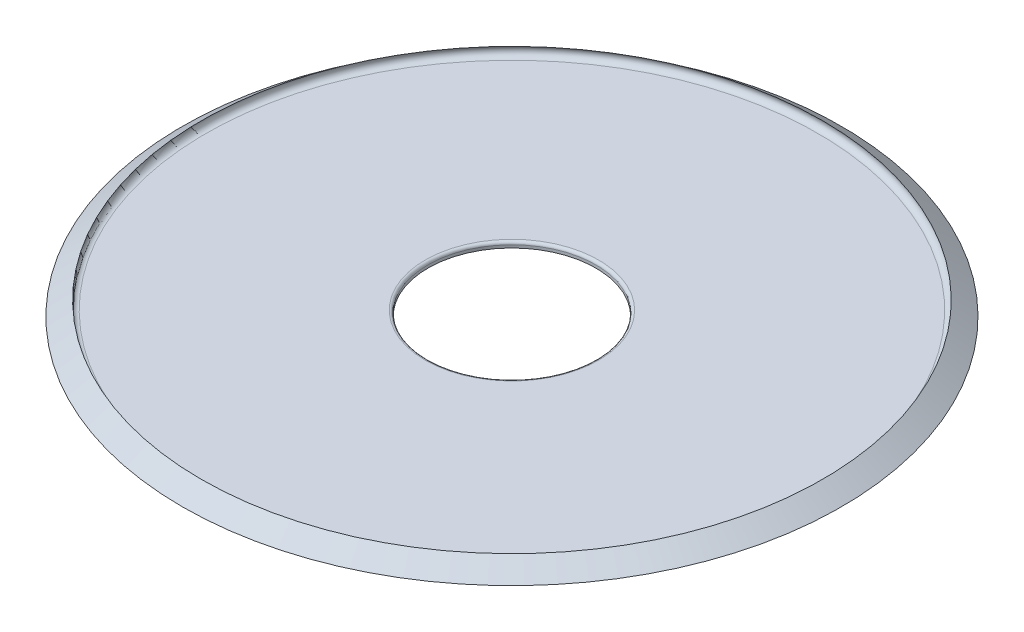
SolidWorks part; units mm, degrees
ref_plane "Front" through (0, 0, 0) normal (0, 0, 1) x (1, 0, 0)
ref_plane "Top" through (0, 0, 0) normal (0, 1, 0) x (1, 0, 0)
ref_plane "Right" through (0, 0, 0) normal (1, 0, 0) x (0, 0, -1)
sketch "Sketch6"
  line L0 (0, 6.1332) -> (0, -2.0816) construction
  line L1 (5.5482, 4.3361) -> (5.8861, 4.08)
  line L2 (1.55, 4.18) -> (5.4653, 4.18)
  line L3 (1.5, 4.13) -> (1.5, 4.08)
  line L4 (1.5, 4.08) -> (5.4929, 4.08)
  line L5 (5.4929, 4.08) -> (5.8861, 4.08)
  line L10 (5.5482, 4.3361) -> (5.8861, 4.08)
  line L11 (5.4929, 4.08) -> (5.8861, 4.08)
  line L12 (0, -16.52) -> (0, -60.6715) construction
  arc A0 (1.5, 4.13) -> (1.55, 4.18) centre (1.55, 4.13) cw
  arc A9 (5.4653, 4.18) -> (5.5482, 4.3361) centre (5.4653, 4.28) ccw
  dimension "D1" = 0.05
sketch "Sketch6<7>" plane through (0, 0, 0) normal (0, 0, 1) x (1, 0, 0) same geometry as "Sketch6"
revolve "iris" add sketch "Sketch6" angle 360 about L0
sketch "Sketch10" plane through (0, 4.18, 0) normal (0, 1, 0) x (1, 0, 0)
  arc A1 (2.6604, 0) -> (2.038, -1.7101) centre (3.2043, -1.1663) ccw
  arc A2 (2.038, -1.7101) -> (0.462, -2.62) centre (1.705, -2.9531) ccw
  arc A3 (0.462, -2.62) -> (-1.3302, -2.304) centre (-0.5921, -3.3581) ccw
  arc A4 (-1.3302, -2.304) -> (-2.5, -0.9099) centre (-2.6122, -2.1919) ccw
  arc A5 (-2.5, -0.9099) -> (-2.5, 0.9099) centre (-3.4099, 0) ccw
  arc A6 (-2.5, 0.9099) -> (-1.3302, 2.304) centre (-2.6122, 2.1919) ccw
  arc A7 (-1.3302, 2.304) -> (0.462, 2.62) centre (-0.5921, 3.3581) ccw
  arc A8 (0.462, 2.62) -> (2.038, 1.7101) centre (1.705, 2.9531) ccw
  arc A9 (2.038, 1.7101) -> (2.6604, 0) centre (3.2043, 1.1663) ccw
  dimension "D1" = 9
sketch "Sketch11" plane through (0, 4.18, 0) normal (0, 1, 0) x (1, 0, 0)
  line L0 (2.6604, 0) -> (5.4653, 0)
  line L1 (2.5, -0.9099) -> (5.1357, -1.8693)
  line L2 (2.038, -1.7101) -> (4.1867, -3.5131)
  line L3 (1.3302, -2.304) -> (2.7327, -4.7331)
  line L4 (0.462, -2.62) -> (0.949, -5.3823)
  line L5 (-0.462, -2.62) -> (-0.949, -5.3823)
  line L6 (-1.3302, -2.304) -> (-2.7327, -4.7331)
  line L7 (-2.038, -1.7101) -> (-4.1867, -3.5131)
  line L8 (-2.5, -0.9099) -> (-5.1357, -1.8693)
  line L9 (-2.6604, 0) -> (-5.4653, 0)
  line L10 (-2.5, 0.9099) -> (-5.1357, 1.8693)
  line L11 (-2.038, 1.7101) -> (-4.1867, 3.5131)
  line L12 (-1.3302, 2.304) -> (-2.7327, 4.7331)
  line L13 (-0.462, 2.62) -> (-0.949, 5.3823)
  line L14 (0.462, 2.62) -> (0.949, 5.3823)
  line L15 (1.3302, 2.304) -> (2.7327, 4.7331)
  line L16 (2.038, 1.7101) -> (4.1867, 3.5131)
  line L17 (2.5, 0.9099) -> (5.1357, 1.8693)
  circle A0 centre (0, 0) radius 5.4653 construction
  dimension "D1" = 18
